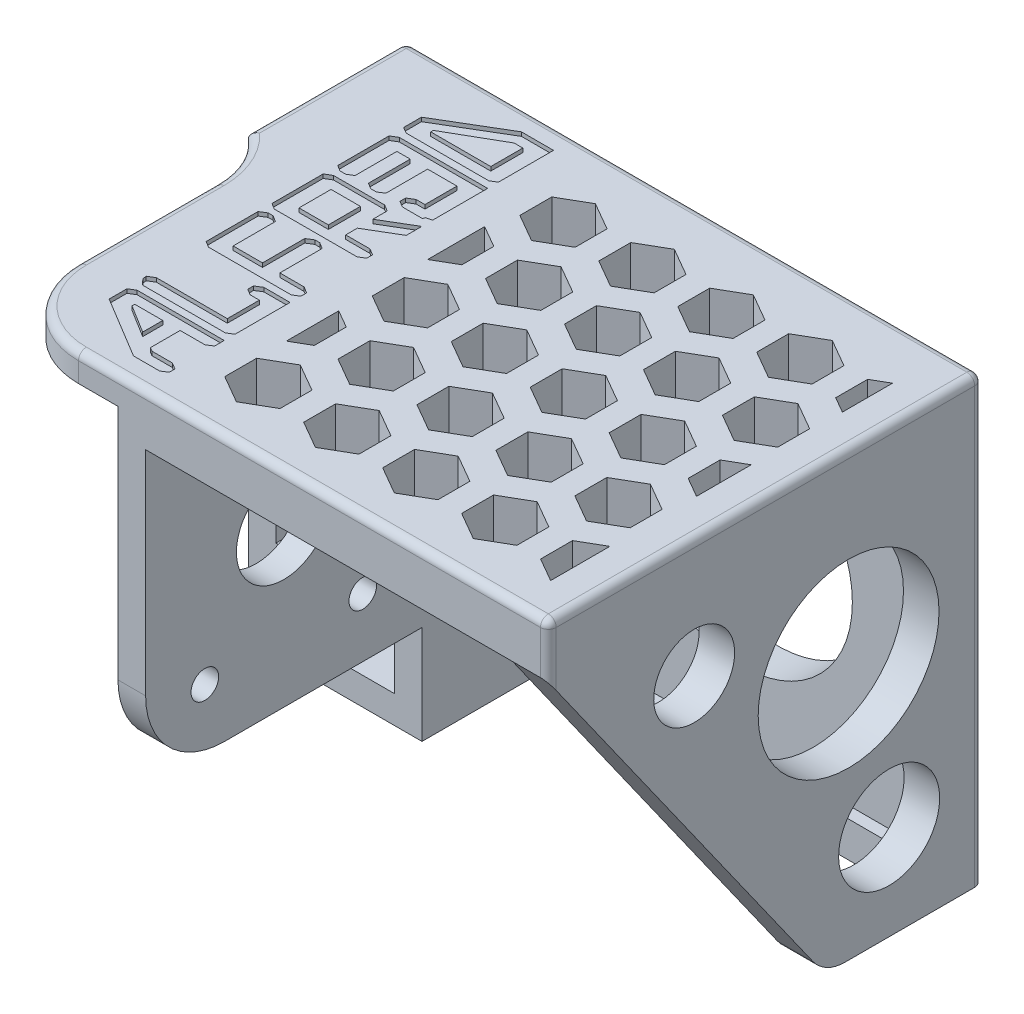
SolidWorks part; units mm, degrees
ref_plane "Front Plane" through (0, 0, 0) normal (0, 0, 1) x (1, 0, 0)
ref_plane "Top Plane" through (0, 0, 0) normal (0, 1, 0) x (1, 0, 0)
ref_plane "Right Plane" through (0, 0, 0) normal (1, 0, 0) x (0, 0, -1)
sketch "Sketch1" plane through (0, 0, 0) normal (0, 0, 1) x (1, 0, 0)
  line L0 (-36.7771, -12.6028) -> (36.2229, -12.6028)
  line L1 (-36.7771, 43.3972) -> (-14.7771, 43.3972)
  line L2 (-36.7771, 43.3972) -> (-36.7771, -12.6028)
  line L3 (36.2229, -12.6028) -> (36.2229, 43.3972)
  line L5 (-33.2771, 39.8972) -> (-18.2771, 39.8972)
  line L6 (-33.2771, 39.8972) -> (-33.2771, 24.8972)
  line L7 (-33.2771, 24.8972) -> (-18.2771, 24.8972)
  line L8 (-18.2771, 39.8972) -> (-18.2771, 24.8972)
  line L9 (-14.7771, 43.3972) -> (36.2229, 43.3972)
  dimension "D1" = 22
  dimension "D3" = 15
  dimension "D4" = 15
  dimension "D5" = 3.5
  dimension "D6" = 51
  dimension "D11" = 3.5
extrude "Boss-Extrude2" add sketch "Sketch1" along normal blind 20 contours L3 L9 L1 L2 L5 L8 L7 L6 region at (1.2081, 14.407, 0)
sketch "Sketch2" plane through (0, 0, 20) normal (0, 0, 1) x (1, 0, 0)
  line L0 (36.2229, -12.6028) -> (36.2229, 43.3972) construction
  line L1 (31.7229, -8.1028) -> (-11.2771, -8.1028)
  line L2 (31.7229, -8.1028) -> (31.7229, 36.8972)
  line L3 (31.7229, 36.8972) -> (-11.2771, 36.8972)
  line L4 (-11.2771, -8.1028) -> (-11.2771, 36.8972)
  line L5 (-36.7771, -12.6028) -> (36.2229, -12.6028) construction
  line L6 (-14.7771, 43.3972) -> (-14.7771, -12.6028) construction
  line L7 (-36.7771, 43.3972) -> (36.2229, 43.3972) construction
  line L8 (-18.2771, 39.8972) -> (-18.2771, 24.8972) construction
  line L9 (-33.2771, 24.8972) -> (-18.2771, 24.8972) construction
  line L10 (-33.2771, 14.8972) -> (-18.2771, 14.8972)
  line L11 (-33.2771, 14.8972) -> (-33.2771, -0.1028)
  line L12 (-33.2771, -0.1028) -> (-18.2771, -0.1028)
  line L13 (-18.2771, 14.8972) -> (-18.2771, -0.1028)
  line L14 (-36.7771, 43.3972) -> (-36.7771, -12.6028) construction
  dimension "D1" = 45
  dimension "D2" = 4.5
  dimension "D3" = 4.5
  dimension "D4" = 3.5
  dimension "D5" = 15
  dimension "D6" = 10
  dimension "D7" = 3.5
  dimension "D8" = 15
  dimension "D9" = 43
extrude "Cut-Extrude1" cut sketch "Sketch2" against normal offset from surface (15.5 mm away) 4.5 up to face at (-0.2771, 15.3972, 0)
sketch "Sketch3" plane through (0, 0, 4.5) normal (0, 0, 1) x (1, 0, 0)
  line L0 (-11.2771, -8.1028) -> (31.7229, 36.8972) construction
  line L1 (-11.2771, 36.8972) -> (31.7229, -8.1028) construction
  circle A0 centre (10.2229, 14.3972) radius 14
  circle A1 centre (25.7229, 30.6181) radius 1.75
  circle A2 centre (-5.2771, 30.6181) radius 1.75
  circle A3 centre (-5.2771, -1.8238) radius 1.75
  circle A4 centre (25.7229, -1.8238) radius 1.75
  dimension "D1" = 28
  dimension "D2" = 3.5
  dimension "D3" = 31
extrude "Cut-Extrude2" cut sketch "Sketch3" against normal blind 4.5
sketch "Sketch5" plane through (0, 0, 20) normal (0, 0, 1) x (1, 0, 0)
  line L0 (-33.2771, 39.8972) -> (-33.2771, 43.3972)
  line L1 (-33.2771, 43.3972) -> (-18.2771, 43.3972)
  line L2 (36.2229, -12.6028) -> (36.2229, 43.3972) construction
  line L3 (-33.2771, 39.8972) -> (-18.2771, 39.8972)
  line L4 (-14.7771, 43.3972) -> (36.2229, 43.3972)
  line L5 (-18.2771, 43.3972) -> (-14.7771, 43.3972)
  line L6 (-18.2771, 39.8972) -> (-18.2771, -0.1028)
  line L7 (-18.2771, -0.1028) -> (-14.7771, -0.1028)
  line L8 (-14.7771, 36.8972) -> (-14.7771, -0.1028)
  line L9 (31.7229, 36.8972) -> (-11.2771, 36.8972) construction
  line L10 (-14.7771, 36.8972) -> (36.2229, 36.8972)
  line L11 (36.2229, 43.3972) -> (36.2229, 36.8972)
  dimension "D1" = 3.5
extrude "Boss-Extrude3" add sketch "Sketch5" along normal blind 35
sketch "Sketch8" plane through (-18.2771, 0, 0) normal (-1, 0, 0) x (0, 0, 1)
  line L0 (20, 24.8972) -> (55, 24.8972) construction
  line L1 (55, 39.8972) -> (55, -0.1028) construction
  line L2 (20, 14.8972) -> (55, 14.8972) construction
  line L3 (55, 32.3972) -> (20, 32.3972) construction
  line L4 (20, 43.3972) -> (20, -12.6028) construction
  line L5 (55, 7.3972) -> (23.2569, 7.3972) construction
  circle A0 centre (37.5, 19.8972) radius 6
  circle A1 centre (27.5, 32.3972) radius 1.75
  circle A2 centre (27.5, 7.3972) radius 1.75
  circle A3 centre (47.5, 7.3972) radius 1.75
  circle A4 centre (47.5, 32.3972) radius 1.75
  dimension "D2" = 12
  dimension "D7" = 17.5
  dimension "D8" = 3.5
  dimension "D1" = 5
  dimension "D3" = 20
  dimension "D4" = 20
  dimension "D5" = 7.5
  dimension "D6" = 7.5
  dimension "D9" = 7.5
  dimension "D10" = 7.5
extrude "Cut-Extrude5" cut sketch "Sketch8" against normal blind 4
sketch "Sketch9" plane through (0, 0, 20) normal (0, 0, 1) x (1, 0, 0)
  line L0 (-36.7771, -12.6028) -> (36.2229, -12.6028) construction
  line L1 (-11.2771, -8.1028) -> (31.7229, -8.1028)
  line L2 (-11.2771, -8.1028) -> (-11.2771, -12.6028)
  line L3 (-11.2771, -12.6028) -> (31.7229, -12.6028)
  line L4 (31.7229, -8.1028) -> (31.7229, -12.6028)
  line L5 (36.2229, -12.6028) -> (36.2229, 36.8972) construction
  dimension "D1" = 4.5
extrude "Cut-Extrude6" cut sketch "Sketch9" against normal offset from surface (14 mm away) 6 up to face at (27.4729, -1.8238, 0)
fillet "Fillet2" radius 10 1 edges at (-16.5271, -0.1028, 55)
sketch "Sketch11" plane through (36.2229, 0, 0) normal (1, 0, 0) x (0, 0, -1)
  line L0 (-55, 36.8972) -> (-20, -12.6028)
  line L1 (-20, -12.6028) -> (-20, 36.8972)
  line L2 (-20, 36.8972) -> (-55, 36.8972)
extrude "Boss-Extrude4" add sketch "Sketch11" against normal up to surface (4.5 mm away) up to face at (31.7229, 1.2722, 8.875)
fillet "Fillet3" radius 10 2 edges at (-33.2771, 41.6472, 55)
sketch "Sketch12" plane through (0, 0, 20) normal (0, 0, 1) x (1, 0, 0)
  line L1 (-14.7771, 36.8972) -> (-11.2771, 36.8972)
  line L2 (-14.7771, 36.8972) -> (-14.7771, -12.6028)
  line L3 (-14.7771, -12.6028) -> (-11.2771, -12.6028)
  line L4 (-11.2771, 36.8972) -> (-11.2771, -12.6028)
extrude "Cut-Extrude8" cut sketch "Sketch12" against normal offset from surface (14 mm away) 6 up to face at (27.4729, -1.8238, 0)
sketch "Sketch13" plane through (0, 43.3972, 0) normal (0, 1, 0) x (1, 0, 0)
  line L0 (-15.2771, 0) -> (-15.2771, -55) construction
  line L1 (-36.7771, 0) -> (36.2229, 0) construction
  line L2 (36.2229, -55) -> (-23.2771, -55) construction
  line L4 (-36.7771, -20) -> (-36.7771, 0) construction
  text T0 "ALFR3D" font "Murder Of Mayday" height 12
  dimension "D1" = 21.5
extrude "Cut-Extrude9" cut sketch "Sketch13" against normal blind 0.5
sketch "Sketch15" plane through (36.2229, 0, 0) normal (1, 0, 0) x (0, 0, -1)
  line L1 (0, 36.8972) -> (-55, 36.8972) construction
  line L2 (0, -12.6028) -> (0, 43.3972) construction
  line L3 (-55, 36.8972) -> (-20, -12.6028) construction
  line L5 (0, 36.8972) -> (-32.2189, 4.6782) construction
  circle A1 centre (-16.9744, 19.9227) radius 11.4509
  circle A2 centre (-36.5312, 28.349) radius 5.1237
  circle A4 centre (-11.8417, -0.5902) radius 6.397
  dimension "D1" = 45
sketch "Sketch18" plane through (0, 43.3972, 0) normal (0, 1, 0) x (1, 0, 0)
  line L0 (-11.2771, -55) -> (-11.2771, -6) construction
  line L1 (36.2229, -55) -> (-23.2771, -55) construction
  line L2 (-11.2771, -50.5) -> (31.7229, -50.5) construction
  line L3 (31.7229, -4.5) -> (31.7229, -55) construction
  line L4 (31.7229, -6) -> (31.7229, -50.5) construction
  line L5 (-11.2771, -6) -> (31.7229, -6) construction
  line L6 (-11.2771, -44.4378) -> (-11.2771, -48.4793) construction
  line L7 (-7.7771, -42.4171) -> (-11.2771, -44.4378)
  line L8 (-11.2771, -44.4378) -> (-11.2771, -48.4793)
  line L9 (-11.2771, -48.4793) -> (-7.7771, -50.5)
  line L10 (-7.7771, -50.5) -> (-4.2771, -48.4793)
  line L11 (-4.2771, -48.4793) -> (-4.2771, -44.4378)
  line L12 (-4.2771, -44.4378) -> (-7.7771, -42.4171)
  line L13 (-2.5271, -33.3238) -> (-6.0271, -35.3446)
  line L14 (0.9729, -35.3446) -> (-2.5271, -33.3238)
  line L15 (0.9729, -39.386) -> (0.9729, -35.3446)
  line L16 (-2.5271, -41.4067) -> (0.9729, -39.386)
  line L17 (-6.0271, -35.3446) -> (-6.0271, -39.386)
  line L18 (-6.0271, -39.386) -> (-2.5271, -41.4067)
  line L19 (2.7229, -24.2306) -> (-0.7771, -26.2513)
  line L20 (6.2229, -26.2513) -> (2.7229, -24.2306)
  line L21 (6.2229, -30.2927) -> (6.2229, -26.2513)
  line L22 (2.7229, -32.3135) -> (6.2229, -30.2927)
  line L23 (-0.7771, -26.2513) -> (-0.7771, -30.2927)
  line L24 (-0.7771, -30.2927) -> (2.7229, -32.3135)
  line L25 (7.9729, -15.1373) -> (4.4729, -17.158)
  line L26 (11.4729, -17.158) -> (7.9729, -15.1373)
  line L27 (11.4729, -21.1995) -> (11.4729, -17.158)
  line L28 (7.9729, -23.2202) -> (11.4729, -21.1995)
  line L29 (4.4729, -17.158) -> (4.4729, -21.1995)
  line L30 (4.4729, -21.1995) -> (7.9729, -23.2202)
  line L31 (13.2229, -6.044) -> (9.7229, -8.0648)
  line L32 (16.7229, -8.0648) -> (13.2229, -6.044)
  line L33 (16.7229, -12.1062) -> (16.7229, -8.0648)
  line L34 (13.2229, -14.1269) -> (16.7229, -12.1062)
  line L35 (9.7229, -8.0648) -> (9.7229, -12.1062)
  line L36 (9.7229, -12.1062) -> (13.2229, -14.1269)
  line L37 (2.2229, -42.4171) -> (-1.2771, -44.4378)
  line L38 (5.7229, -44.4378) -> (2.2229, -42.4171)
  line L39 (5.7229, -48.4793) -> (5.7229, -44.4378)
  line L40 (2.2229, -50.5) -> (5.7229, -48.4793)
  line L41 (-1.2771, -44.4378) -> (-1.2771, -48.4793)
  line L42 (-1.2771, -48.4793) -> (2.2229, -50.5)
  line L43 (3.9729, -39.386) -> (7.4729, -41.4067)
  line L44 (7.4729, -41.4067) -> (10.9729, -39.386)
  line L45 (10.9729, -39.386) -> (10.9729, -35.3446)
  line L46 (10.9729, -35.3446) -> (7.4729, -33.3238)
  line L47 (7.4729, -33.3238) -> (3.9729, -35.3446)
  line L48 (9.2229, -26.2513) -> (9.2229, -30.2927)
  line L49 (12.7229, -24.2306) -> (9.2229, -26.2513)
  line L50 (16.2229, -26.2513) -> (12.7229, -24.2306)
  line L51 (16.2229, -30.2927) -> (16.2229, -26.2513)
  line L52 (12.7229, -32.3135) -> (16.2229, -30.2927)
  line L53 (9.2229, -30.2927) -> (12.7229, -32.3135)
  line L54 (14.4729, -21.1995) -> (17.9729, -23.2202)
  line L55 (14.4729, -17.158) -> (14.4729, -21.1995)
  line L56 (17.9729, -23.2202) -> (21.4729, -21.1995)
  line L57 (21.4729, -21.1995) -> (21.4729, -17.158)
  line L58 (21.4729, -17.158) -> (17.9729, -15.1373)
  line L59 (17.9729, -15.1373) -> (14.4729, -17.158)
  line L60 (19.7229, -12.1062) -> (23.2229, -14.1269)
  line L61 (19.7229, -8.0648) -> (19.7229, -12.1062)
  line L62 (23.2229, -6.044) -> (19.7229, -8.0648)
  line L63 (26.7229, -8.0648) -> (23.2229, -6.044)
  line L64 (26.7229, -12.1062) -> (26.7229, -8.0648)
  line L65 (23.2229, -14.1269) -> (26.7229, -12.1062)
  line L66 (3.9729, -35.3446) -> (3.9729, -39.386)
  line L67 (12.2229, -42.4171) -> (8.7229, -44.4378)
  line L68 (15.7229, -44.4378) -> (12.2229, -42.4171)
  line L69 (15.7229, -48.4793) -> (15.7229, -44.4378)
  line L70 (12.2229, -50.5) -> (15.7229, -48.4793)
  line L71 (8.7229, -44.4378) -> (8.7229, -48.4793)
  line L72 (8.7229, -48.4793) -> (12.2229, -50.5)
  line L73 (13.9729, -39.386) -> (17.4729, -41.4067)
  line L74 (17.4729, -41.4067) -> (20.9729, -39.386)
  line L75 (20.9729, -39.386) -> (20.9729, -35.3446)
  line L76 (20.9729, -35.3446) -> (17.4729, -33.3238)
  line L77 (17.4729, -33.3238) -> (13.9729, -35.3446)
  line L78 (19.2229, -26.2513) -> (19.2229, -30.2927)
  line L79 (22.7229, -24.2306) -> (19.2229, -26.2513)
  line L80 (26.2229, -26.2513) -> (22.7229, -24.2306)
  line L81 (26.2229, -30.2927) -> (26.2229, -26.2513)
  line L82 (22.7229, -32.3135) -> (26.2229, -30.2927)
  line L83 (19.2229, -30.2927) -> (22.7229, -32.3135)
  line L84 (24.4729, -21.1995) -> (27.9729, -23.2202)
  line L85 (24.4729, -17.158) -> (24.4729, -21.1995)
  line L86 (27.9729, -23.2202) -> (31.4729, -21.1995)
  line L87 (31.4729, -21.1995) -> (31.4729, -17.158)
  line L88 (31.4729, -17.158) -> (27.9729, -15.1373)
  line L89 (27.9729, -15.1373) -> (24.4729, -17.158)
  line L90 (29.7229, -12.1062) -> (31.7229, -13.2609)
  line L91 (29.7229, -8.0648) -> (29.7229, -12.1062)
  line L92 (31.7229, -6.9101) -> (29.7229, -8.0648)
  line L93 (-11.2771, -15.5703) -> (-11.2771, -22.7872)
  line L94 (-11.2771, -34.0455) -> (-11.2771, -40.685)
  line L95 (31.7229, -50.2113) -> (31.7229, -42.7058)
  line L96 (13.9729, -35.3446) -> (13.9729, -39.386)
  line L97 (22.2229, -42.4171) -> (18.7229, -44.4378)
  line L98 (25.7229, -44.4378) -> (22.2229, -42.4171)
  line L99 (25.7229, -48.4793) -> (25.7229, -44.4378)
  line L100 (22.2229, -50.5) -> (25.7229, -48.4793)
  line L101 (18.7229, -44.4378) -> (18.7229, -48.4793)
  line L102 (18.7229, -48.4793) -> (22.2229, -50.5)
  line L103 (23.9729, -39.386) -> (27.4729, -41.4067)
  line L104 (27.4729, -41.4067) -> (30.9729, -39.386)
  line L105 (30.9729, -39.386) -> (30.9729, -35.3446)
  line L106 (30.9729, -35.3446) -> (27.4729, -33.3238)
  line L107 (27.4729, -33.3238) -> (23.9729, -35.3446)
  line L108 (29.2229, -26.2513) -> (29.2229, -30.2927)
  line L109 (31.7229, -24.8079) -> (29.2229, -26.2513)
  line L110 (31.7229, -31.7361) -> (31.7229, -24.8079)
  line L111 (31.7229, -13.2609) -> (31.7229, -6.9101)
  line L113 (29.2229, -30.2927) -> (31.7229, -31.7361)
  line L126 (23.9729, -35.3446) -> (23.9729, -39.386)
  line L127 (31.7229, -42.7058) -> (28.7229, -44.4378)
  line L131 (28.7229, -44.4378) -> (28.7229, -48.4793)
  line L132 (28.7229, -48.4793) -> (31.7229, -50.2113)
  line L164 (-11.2771, -40.685) -> (-9.0271, -39.386)
  line L165 (-9.0271, -39.386) -> (-9.0271, -35.3446)
  line L166 (-9.0271, -35.3446) -> (-11.2771, -34.0455)
  line L168 (-10.7771, -26.2513) -> (-10.7771, -30.2927)
  line L169 (-7.2771, -24.2306) -> (-10.7771, -26.2513)
  line L170 (-3.7771, -26.2513) -> (-7.2771, -24.2306)
  line L171 (-3.7771, -30.2927) -> (-3.7771, -26.2513)
  line L172 (-7.2771, -32.3135) -> (-3.7771, -30.2927)
  line L173 (-10.7771, -30.2927) -> (-7.2771, -32.3135)
  line L174 (-5.5271, -21.1995) -> (-2.0271, -23.2202)
  line L175 (-5.5271, -17.158) -> (-5.5271, -21.1995)
  line L176 (-2.0271, -23.2202) -> (1.4729, -21.1995)
  line L177 (1.4729, -21.1995) -> (1.4729, -17.158)
  line L178 (1.4729, -17.158) -> (-2.0271, -15.1373)
  line L179 (-2.0271, -15.1373) -> (-5.5271, -17.158)
  line L180 (-0.2771, -12.1062) -> (3.2229, -14.1269)
  line L181 (-0.2771, -8.0648) -> (-0.2771, -12.1062)
  line L182 (3.2229, -6.044) -> (-0.2771, -8.0648)
  line L183 (6.7229, -8.0648) -> (3.2229, -6.044)
  line L184 (6.7229, -12.1062) -> (6.7229, -8.0648)
  line L185 (3.2229, -14.1269) -> (6.7229, -12.1062)
  line L206 (-11.2771, -22.7872) -> (-8.5271, -21.1995)
  line L207 (-8.5271, -21.1995) -> (-8.5271, -17.158)
  line L208 (-8.5271, -17.158) -> (-11.2771, -15.5703)
  line L210 (-10.2771, -12.1062) -> (-6.7771, -14.1269)
  line L211 (-10.2771, -8.0648) -> (-10.2771, -12.1062)
  line L212 (-6.7771, -6.044) -> (-10.2771, -8.0648)
  line L213 (-3.2771, -8.0648) -> (-6.7771, -6.044)
  line L214 (-3.2771, -12.1062) -> (-3.2771, -8.0648)
  line L215 (-6.7771, -14.1269) -> (-3.2771, -12.1062)
  line L519 (46.7229, -8.0648) -> (43.2229, -6.044) [skipped]
  line L520 (46.7229, -12.1062) -> (46.7229, -8.0648) [skipped]
  line L521 (49.7229, -8.0648) -> (49.7229, -12.1062) [skipped]
  line L522 (53.2229, -6.044) -> (49.7229, -8.0648) [skipped]
  line L523 (56.7229, -8.0648) -> (53.2229, -6.044) [skipped]
  line L524 (56.7229, -12.1062) -> (56.7229, -8.0648) [skipped]
  line L525 (53.2229, -14.1269) -> (56.7229, -12.1062) [skipped]
  line L526 (49.7229, -12.1062) -> (53.2229, -14.1269) [skipped]
  line L527 (43.2229, -14.1269) -> (46.7229, -12.1062) [skipped]
  line L528 (39.7229, -12.1062) -> (43.2229, -14.1269) [skipped]
  line L529 (43.2229, -6.044) -> (39.7229, -8.0648) [skipped]
  line L530 (39.7229, -8.0648) -> (39.7229, -12.1062) [skipped]
  line L531 (41.4729, -17.158) -> (37.9729, -15.1373) [skipped]
  line L532 (41.4729, -21.1995) -> (41.4729, -17.158) [skipped]
  line L533 (44.4729, -17.158) -> (44.4729, -21.1995) [skipped]
  line L534 (47.9729, -15.1373) -> (44.4729, -17.158) [skipped]
  line L535 (51.4729, -17.158) -> (47.9729, -15.1373) [skipped]
  line L536 (51.4729, -21.1995) -> (51.4729, -17.158) [skipped]
  line L537 (47.9729, -23.2202) -> (51.4729, -21.1995) [skipped]
  line L538 (44.4729, -21.1995) -> (47.9729, -23.2202) [skipped]
  line L539 (37.9729, -23.2202) -> (41.4729, -21.1995) [skipped]
  line L540 (42.7229, -24.2306) -> (39.2229, -26.2513) [skipped]
  line L541 (46.2229, -26.2513) -> (42.7229, -24.2306) [skipped]
  line L542 (46.2229, -30.2927) -> (46.2229, -26.2513) [skipped]
  line L543 (39.2229, -26.2513) -> (39.2229, -30.2927) [skipped]
  line L544 (39.2229, -30.2927) -> (42.7229, -32.3135) [skipped]
  line L545 (42.7229, -32.3135) -> (46.2229, -30.2927) [skipped]
  line L546 (40.9729, -35.3446) -> (37.4729, -33.3238) [skipped]
  line L547 (40.9729, -39.386) -> (40.9729, -35.3446) [skipped]
  line L548 (37.4729, -41.4067) -> (40.9729, -39.386) [skipped]
  line L549 (36.7229, -8.0648) -> (33.2229, -6.044) [skipped]
  line L550 (33.2229, -14.1269) -> (36.7229, -12.1062) [skipped]
  line L551 (37.9729, -15.1373) -> (34.4729, -17.158) [skipped]
  line L552 (36.7229, -12.1062) -> (36.7229, -8.0648) [skipped]
  line L553 (34.4729, -21.1995) -> (37.9729, -23.2202) [skipped]
  line L554 (34.4729, -17.158) -> (34.4729, -21.1995) [skipped]
  line L555 (36.2229, -26.2513) -> (32.7229, -24.2306) [skipped]
  line L556 (32.7229, -32.3135) -> (36.2229, -30.2927) [skipped]
  line L557 (36.2229, -30.2927) -> (36.2229, -26.2513) [skipped]
  line L558 (37.4729, -33.3238) -> (33.9729, -35.3446) [skipped]
  line L559 (33.9729, -39.386) -> (37.4729, -41.4067) [skipped]
  line L560 (32.2229, -50.5) -> (35.7229, -48.4793) [skipped]
  line L561 (35.7229, -48.4793) -> (35.7229, -44.4378) [skipped]
  line L562 (35.7229, -44.4378) -> (32.2229, -42.4171) [skipped]
  line L563 (33.9729, -35.3446) -> (33.9729, -39.386) [skipped]
  line L564 (-31.2771, -48.4793) -> (-27.7771, -50.5) [skipped]
  line L565 (-31.2771, -44.4378) -> (-31.2771, -48.4793) [skipped]
  line L566 (-27.7771, -42.4171) -> (-31.2771, -44.4378) [skipped]
  line L567 (-24.2771, -44.4378) -> (-27.7771, -42.4171) [skipped]
  line L568 (-26.0271, -39.386) -> (-22.5271, -41.4067) [skipped]
  line L569 (-26.0271, -35.3446) -> (-26.0271, -39.386) [skipped]
  line L570 (-22.5271, -33.3238) -> (-26.0271, -35.3446) [skipped]
  line L571 (-19.0271, -35.3446) -> (-22.5271, -33.3238) [skipped]
  line L572 (-20.7771, -30.2927) -> (-17.2771, -32.3135) [skipped]
  line L573 (-17.2771, -24.2306) -> (-20.7771, -26.2513) [skipped]
  line L574 (-20.7771, -26.2513) -> (-20.7771, -30.2927) [skipped]
  line L575 (-15.5271, -21.1995) -> (-12.0271, -23.2202) [skipped]
  line L576 (-12.0271, -15.1373) -> (-15.5271, -17.158) [skipped]
  line L577 (-15.5271, -17.158) -> (-15.5271, -21.1995) [skipped]
  line L578 (-13.7771, -26.2513) -> (-17.2771, -24.2306) [skipped]
  line L579 (-17.2771, -32.3135) -> (-13.7771, -30.2927) [skipped]
  line L580 (-13.7771, -30.2927) -> (-13.7771, -26.2513) [skipped]
  line L581 (-19.0271, -39.386) -> (-19.0271, -35.3446) [skipped]
  line L582 (-22.5271, -41.4067) -> (-19.0271, -39.386) [skipped]
  line L583 (-24.2771, -48.4793) -> (-24.2771, -44.4378) [skipped]
  line L584 (-27.7771, -50.5) -> (-24.2771, -48.4793) [skipped]
  line L585 (-21.2771, -44.4378) -> (-21.2771, -48.4793) [skipped]
  line L586 (-21.2771, -48.4793) -> (-17.7771, -50.5) [skipped]
  line L587 (-17.7771, -50.5) -> (-14.2771, -48.4793) [skipped]
  line L588 (-14.2771, -48.4793) -> (-14.2771, -44.4378) [skipped]
  line L589 (-14.2771, -44.4378) -> (-17.7771, -42.4171) [skipped]
  line L590 (-17.7771, -42.4171) -> (-21.2771, -44.4378) [skipped]
  line L591 (-16.0271, -39.386) -> (-12.5271, -41.4067) [skipped]
  line L592 (-16.0271, -35.3446) -> (-16.0271, -39.386) [skipped]
  line L593 (-12.5271, -33.3238) -> (-16.0271, -35.3446) [skipped]
  circle A0 centre (-7.7771, -46.4585) radius 3.5 construction
  dimension "D2" = 7
  dimension "D1" = 4.5
  dimension "D3" = 5
  dimension "D4" = 5
  dimension "D5" = 3
extrude "Cut-Extrude15" cut sketch "Sketch18" against normal blind 10
extrude "Cut-Extrude10" cut sketch "Sketch15" against normal blind 4.5
sketch "Sketch17" plane through (0, 0, 20) normal (0, 0, 1) x (1, 0, 0)
  line L1 (-33.2771, -3.6028) -> (-18.2771, -3.6028)
  line L2 (-33.2771, -3.6028) -> (-33.2771, -9.1028)
  line L3 (-33.2771, -9.1028) -> (-18.2771, -9.1028)
  line L4 (-18.2771, -3.6028) -> (-18.2771, -9.1028)
  line L10 (-36.7771, 39.8972) -> (-36.7771, -12.6028) construction
  line L11 (-33.2771, -0.1028) -> (-18.2771, -0.1028) construction
  line L12 (-36.7771, -12.6028) -> (-14.7771, -12.6028) construction
  line L13 (-14.7771, -0.1028) -> (-14.7771, -12.6028) construction
  dimension "D5" = 3.5
  dimension "D6" = 3.5
  dimension "D7" = 3.5
  dimension "D8" = 3.5
extrude "Cut-Extrude12" cut sketch "Sketch17" against normal offset from surface (15.5 mm away) 4.5 up to face at (27.4729, -1.8238, 0)
fillet "Fillet5" radius 1 8 edges at (-34.1942, 43.3972, 23.416) (-30.3482, 43.3972, 52.0711) (-36.7771, 43.3972, 10) (6.4729, 43.3972, 55) (36.2229, 15.3972, 0) (-0.2771, 43.3972, 0) (36.2229, 43.3972, 27.5)
fillet "Fillet6" radius 1 4 edges at (35.93, 43.1043, 54.7071) (36.2229, 39.6472, 55) (-36.4842, 43.1043, 0.2929) (-36.7771, 14.8972, 0)
fillet "Fillet7" radius 5 1 edges at (33.9729, -12.6028, 20)
